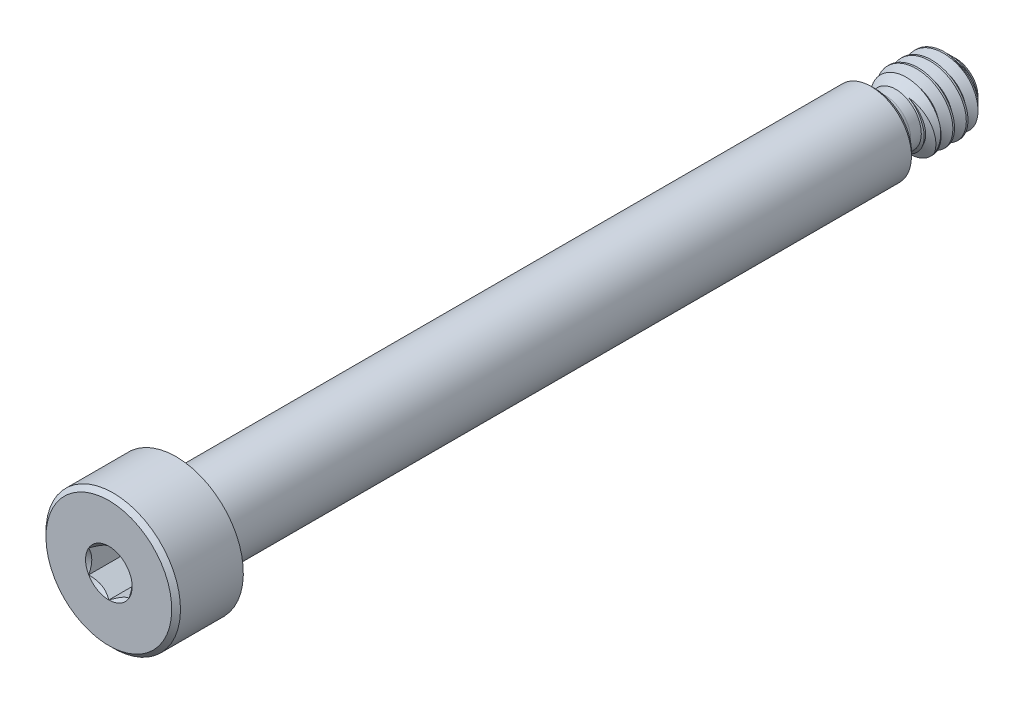
SolidWorks part; units mm, degrees
note: '?' marks a value the reader was unsure of.
other "DetailItem1"
other "DetailItem2"
other "DetailItem5"
other "DetailItem6"
ref_plane "Front" through (0, 0, 0) normal (0, 0, 1) x (1, 0, 0)
ref_plane "Top" through (0, 0, 0) normal (0, 1, 0) x (1, 0, 0)
ref_plane "Right" through (0, 0, 0) normal (1, 0, 0) x (0, 0, -1)
sketch "Sketch1" plane through (0, 0, 0) normal (1, 0, 0) x (0, 0, -1)
  line L0 (-45.2438, 3.9687) -> (-41.275, 3.9687)
  line L1 (-41.275, 3.9687) -> (-41.275, 2.3812)
  line L2 (-41.275, 2.3812) -> (0, 2.3812)
  line L3 (0, 2.3812) -> (0, 2.0828)
  line L4 (0, 2.0828) -> (4.7625, 2.0828)
  line L5 (4.7625, 2.0828) -> (4.7625, 0)
  line L6 (4.7625, 0) -> (-45.2438, 0)
  line L7 (-45.2438, 0) -> (-45.2438, 3.9687)
  line L8 (-45.2438, 3.9687) -> (-45.2438, -3.9688) construction
  line L9 (4.7625, 2.0828) -> (4.7625, -2.0828) construction
  line L10 (0, 2.3812) -> (0, -2.3813) construction
  point P8 (3.5719, -2.0828)
  point P12 (0, 0)
  point P13 (4.7625, 2.3812)
  point P14 (-41.275, 2.3812)
  point P15 (0, 2.3812)
  point P16 (4.7625, -2.3813)
  dimension "Head Dia" = 7.9375
  dimension "Head Ht" = 3.9688
  dimension "Thread Lg" = 4.7625
  dimension "Thread Dia" = 4.1656
  dimension "Shoulder Dia" = 4.7625
  dimension "Shoulder Lg" = 41.275
  dimension "D1" = 1.1906
  dimension "Drawing Shoulder Dia" = 4.7625
revolve "Revolve1" add sketch "Sketch1" angle 360 mid plane about L6
ref_plane "Plane1" through (0, 0, -4.7625) normal (0, 0, 1) x (1, 0, 0)
sketch "Sketch3" plane through (0, 0, -4.7625) normal (0, 0, 1) x (1, 0, 0)
  circle A0 centre (0, 0) radius 2.0828
curve "Helix/Spiral1" pitch 0.7937 height 5.5562 turns 7 parameters "Pitch"=0.7937
sketch "Sketch5" plane through (0, 0, 0) normal (1, 0, 0) x (0, 0, -1)
  line L0 (0, 2.3812) -> (2.0638, 2.3812)
  line L1 (2.0638, 2.3812) -> (1.1938, 1.5113)
  line L2 (1.1938, 1.5113) -> (0.5715, 1.5113)
  line L3 (0, 2.3812) -> (0, 2.0828)
  line L5 (0, 2.0828) -> (4.7625, 2.0828) construction
  line L6 (4.7625, 0) -> (1.1938, 0) construction
  line L7 (2.9781, 0) -> (2.9781, -2.0828) construction
  line L8 (0, -2.3813) -> (0, -2.0828) construction
  line L9 (0.5715, 1.5113) -> (0.5715, -1.5113) construction
  line L10 (1.1938, -1.5113) -> (0.5715, -1.5113) construction
  line L11 (2.0638, -2.3813) -> (1.1938, -1.5113) construction
  line L12 (0, -2.3813) -> (2.0638, -2.3813) construction
  arc A0 (0, 2.0828) -> (0.5715, 1.5113) centre (0.5715, 2.0828) ccw
  arc A1 (0, -2.0828) -> (0.5715, -1.5113) centre (0.5715, -2.0828) cw construction
  point P6 (0.5715, 0)
  dimension "D1" = 45
  dimension "CADB" = 1.1938
  dimension "CADA" = 3.0226
revolve "Cut-Revolve1" cut sketch "Sketch5" angle 360 mid plane about L6
chamfer "Chamfer1" distance 0.7937 angle 45 1 edges at (0, 2.0828, -4.7625)
chamfer "Chamfer2" distance 0.258 angle 45 2 edges at (0, 3.9687, 45.2437) (0, 2.3812, 0)
sketch "Sketch8" plane through (0, 0, 45.2438) normal (0, 0, 1) x (1, 0, 0)
  line L1 (1.1906, 0.6874) -> (0, 1.3748)
  line L2 (0, 1.3748) -> (-1.1906, 0.6874)
  line L3 (-1.1906, 0.6874) -> (-1.1906, -0.6874)
  line L4 (-1.1906, -0.6874) -> (0, -1.3748)
  line L5 (0, -1.3748) -> (1.1906, -0.6874)
  line L6 (1.1906, -0.6874) -> (1.1906, 0.6874)
  circle A0 centre (0, 0) radius 1.1906 construction
  dimension "Hex" = 2.3813
extrude "Cut-Extrude2" cut sketch "Sketch8" against normal blind 1.9844
sketch "Sketch9" plane through (0, 0, 45.2438) normal (0, 0, 1) x (1, 0, 0)
  circle A0 centre (0, 0) radius 1.3748
extrude "Cut-Extrude4" cut sketch "Sketch9" against normal blind 1.9844 draft 45
sketch "reference 1" plane through (0, 0, 41.275) normal (0, 0, -1) x (-1, 0, 0)
  circle A1 centre (0, 0) radius 3.9687
  circle A2 centre (0, 0) radius 3.9687 construction
ref_axis "Center Axis 1" through (0, 0, 41.275) along (0, 0, -1)?
ref_plane "Contact Plane 1" through (0, 0, 0) normal (0, 0, 1) x (1, 0, 0)
ref_plane "Plane2" through (0, 0, -1.1938) normal (0, 0, 1) x (1, 0, 0)
split "Split1" trim tools "Plane2" bodies to split 118 resulting bodies 119 120
sketch "Sketch4" plane through (0, 0, 0) normal (1, 0, 0) x (0, 0, -1)
  line L0 (4.7129, 2.1687) -> (5.1098, 1.4813) construction
  line L1 (5.1098, 1.4813) -> (5.5066, 2.1687) construction
  line L3 (4.7129, 2.1687) -> (5.5066, 2.1687) construction
  line L4 (5.1098, 1.4813) -> (5.1098, 1.5672) construction
  line L5 (5.1098, 2.1687) -> (5.1098, 2.0828) construction
  line L6 (4.7625, 2.0828) -> (5.457, 2.0828) construction
  line L7 (5.0602, 1.5672) -> (5.1594, 1.5672) construction
  line L8 (4.7377, 2.1258) -> (5.4818, 2.1258) construction
  line L9 (4.7377, 2.1258) -> (5.4818, 2.1258)
  line L10 (5.4818, 2.1258) -> (5.1594, 1.5672)
  line L11 (5.1594, 1.5672) -> (5.0602, 1.5672)
  line L12 (5.0602, 1.5672) -> (4.7377, 2.1258)
  point P10 (5.1098, 2.0828)
  point P13 (5.1098, 1.5672)
  point P16 (5.1098, 2.1258)
  dimension "D1" = 0.7937
  dimension "D2" = 0.0992
sweep "Cut-Sweep1" cut profiles "Sketch4" path "Helix/Spiral1" align with end faces yes
combine bodies "Combine1" operation type add bodies to combine 119 121
equation "\"D3@Helix/Spiral1\" = \"Thread Lg@Sketch1\" + \"Pitch@Helix/Spiral1\""
equation "\"D1@Cut-Extrude2\"= \"Head Ht@Sketch1\" * .5"
equation "\"D1@Cut-Extrude4\" = \"D1@Cut-Extrude2\""
equation "\"D1@Chamfer2\" = \"Head Dia@Sketch1\" * .0325"
equation "\"D1@Sketch1\"=\"Pitch@Helix/Spiral1\" * 1.5"
equation "\"D1@Sketch4\" = \"Pitch@Helix/Spiral1\""
equation "\"D2@Sketch4\"=\"D1@Sketch4\"/8"
equation "\"D1@Chamfer1\" = \"Pitch@Helix/Spiral1\""
equation "\"Drawing Shoulder Dia@Sketch1\"=\"Shoulder Dia@Sketch1\""
